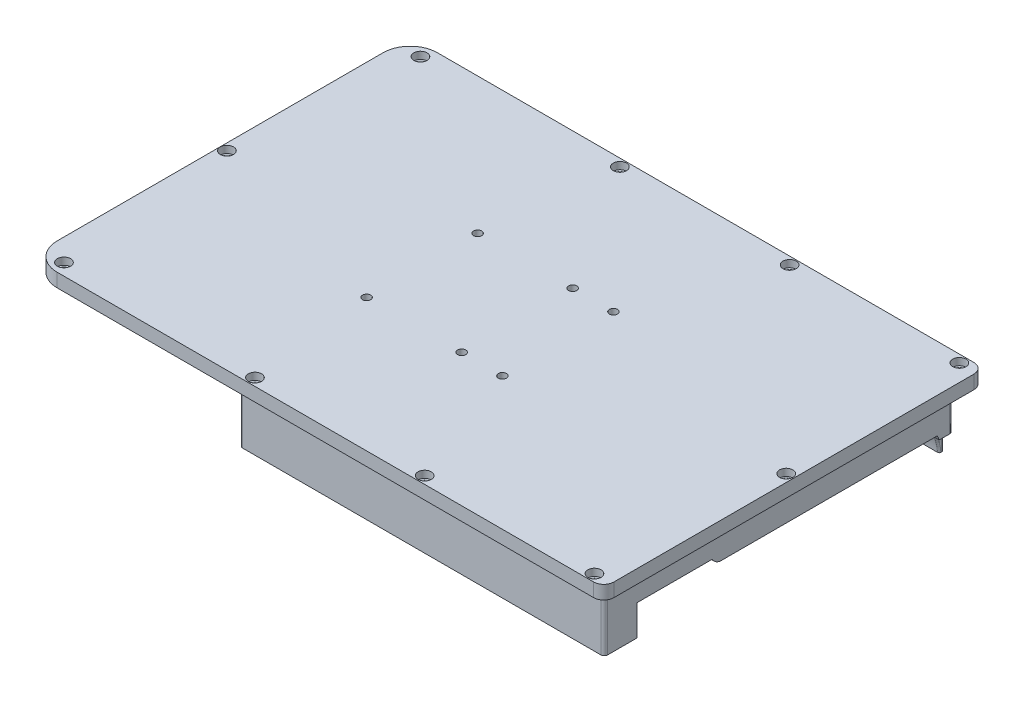
SolidWorks part; units mm, degrees
ref_plane "Front Plane" through (0, 0, 0) normal (0, 0, 1) x (1, 0, 0)
ref_plane "Top Plane" through (0, 0, 0) normal (0, 1, 0) x (1, 0, 0)
ref_plane "Right Plane" through (0, 0, 0) normal (1, 0, 0) x (0, 0, -1)
sketch "Sketch1" plane through (0, 0, 0) normal (0, 1, 0) x (1, 0, 0)
  line L1 (-56, 51.85) -> (56, 51.85)
  line L2 (-56, 51.85) -> (-56, -51.85)
  line L3 (-56, -51.85) -> (56, -51.85)
  line L4 (56, 51.85) -> (56, -51.85)
  line L5 (-56, 51.85) -> (56, -51.85) construction
  line L6 (-56, -51.85) -> (56, 51.85) construction
  point P0 (0, 0)
  dimension "D1" = 103.7
  dimension "D2" = 112
extrude "Boss-Extrude1" add sketch "Sketch1" along normal blind 18.2
ref_plane "Plane1" through (51.5, 0, 0) normal (1, 0, 0) x (0, 0, -1)
sketch "Sketch2" plane through (51.5, 0, 0) normal (1, 0, 0) x (0, 0, -1)
  line L0 (-51.85, 18.2) -> (51.85, 18.2) construction
  line L1 (0, 0) -> (0, -18.713) construction
  circle A0 centre (0, 18.2) radius 16.325
  circle A1 centre (32.65, 18.2) radius 16.325
  circle A2 centre (-32.65, 18.2) radius 16.325
  dimension "D1" = 32.65
  dimension "D2" = 32.65
extrude "Cut-Extrude1" cut sketch "Sketch2" against normal blind 73 contours A0 | A2 | A1 region at (51.5, 18.2, 0) region at (51.5, 18.2, 32.65) region at (51.5, 18.2, -32.65)
fillet "Fillet1" radius 3 2 edges at (15, 18.2, -16.325) (15, 18.2, 16.325)
sketch "Sketch3" plane through (0, 0, 0) normal (0, 0, 1) x (1, 0, 0)
  line L0 (56, 18.2) -> (-56, 18.2) construction
  circle A0 centre (-39, 18.2) radius 16.325
  dimension "D1" = 32.65
  dimension "D2" = 39
extrude "Cut-Extrude2" cut sketch "Sketch3" against normal blind 35.4 and the other way blind 35.4
sketch "Sketch4" plane through (0, 0, -35.4) normal (0, 0, 1) x (1, 0, 0)
  line L0 (-45, 18.2) -> (-45, 9.2)
  line L1 (-55.325, 18.2) -> (-22.675, 18.2) construction
  line L2 (-45, 18.2) -> (-22.675, 18.2)
  line L3 (-45, 9.2) -> (-25.38, 9.2)
  arc A0 (-55.325, 18.2) -> (-22.675, 18.2) centre (-39, 18.2) ccw construction
  arc A1 (-25.38, 9.2) -> (-22.675, 18.2) centre (-39, 18.2) ccw
  dimension "D1" = 9
  dimension "D2" = 6
extrude "Cut-Extrude3" cut sketch "Sketch4" against normal blind 11
mirror "Mirror1" about plane through (0, 0, 0) normal (0, 0, 1) of "Cut-Extrude3"
sketch "Sketch5" plane through (-21.5, 0, 0) normal (1, 0, 0) x (0, 0, -1)
  line L0 (-41.65, 18.2) -> (-41.65, 9.2)
  line L1 (-48.975, 18.2) -> (-16.325, 18.2) construction
  line L2 (-41.65, 9.2) -> (-19.03, 9.2)
  line L3 (-46.4, 9.2) -> (-35.4, 9.2) construction
  line L4 (-41.65, 18.2) -> (-16.325, 18.2)
  line L5 (-16.325, 18.2) -> (16.325, 18.2) construction
  arc A0 (-48.975, 18.2) -> (-18.8593, 9.4638) centre (-32.65, 18.2) ccw construction
  arc A1 (-19.03, 9.2) -> (-18.8593, 9.4638) centre (-32.65, 18.2) ccw
  arc A2 (-18.8593, 9.4638) -> (-16.325, 18.2) centre (-32.65, 18.2) ccw
  dimension "D1" = 9
extrude "Cut-Extrude4" cut sketch "Sketch5" against normal blind 10
fillet "Fillet3" radius 1 8 edges at (-23.3659, 13.5011, 17.0159) (-23.3659, 13.5011, 41.65) (-23.3659, 13.5011, 46.4) (-45, 13.7, 46.4) (-45, 13.7, 35.4) (-23.3659, 13.5011, -46.4) (-45, 13.7, -35.4) (-45, 13.7, -46.4)
sketch "Sketch6" plane through (-45, 0, 0) normal (1, 0, 0) x (0, 0, -1)
  line L0 (45.4, 18.2) -> (36.4, 18.2) construction
  line L2 (46.4, 18.2) -> (46.4, 9.2) construction
  circle A0 centre (42.9, 18.2) radius 3.5
  dimension "D1" = 7
extrude "Cut-Extrude6" cut sketch "Sketch6" against normal through all and the other way blind 1
sketch "Sketch7" plane through (-21.5, 0, 0) normal (1, 0, 0) x (0, 0, -1)
  line L0 (47.231, 10.8583) -> (-16.325, 10.8583)
  arc A0 (18.8593, 9.4638) -> (48.975, 18.2) centre (32.65, 18.2) ccw construction
  arc A1 (18.8593, 9.4638) -> (13.7907, 9.4638) centre (16.325, 7.8583) ccw construction
  arc A2 (-13.7907, 9.4638) -> (13.7907, 9.4638) centre (0, 18.2) ccw construction
  arc A3 (18.8593, 9.4638) -> (47.231, 10.8583) centre (32.65, 18.2) ccw
  arc A4 (18.8593, 9.4638) -> (13.7907, 9.4638) centre (16.325, 7.8583) ccw
  arc A5 (-13.7907, 9.4638) -> (13.7907, 9.4638) centre (0, 18.2) ccw
  arc A6 (-13.7907, 9.4638) -> (-18.8593, 9.4638) centre (-16.325, 7.8583) ccw construction
  arc A7 (-13.7907, 9.4638) -> (-16.325, 10.8583) centre (-16.325, 7.8583) ccw
  arc M4 (-18.8593, 9.4638) -> (-13.7907, 9.4638) centre (-16.325, 7.8583) cw
  arc M5 (-13.7907, 9.4638) -> (13.7907, 9.4638) centre (0, 18.2) ccw
  arc M6 (13.7907, 9.4638) -> (18.8593, 9.4638) centre (16.325, 7.8583) cw
  arc M7 (18.8593, 9.4638) -> (48.975, 18.2) centre (32.65, 18.2) ccw
extrude "Boss-Extrude2" add sketch "Sketch7" along normal blind 1.1 contours L0 M7 M6 | L0 M6 M4 M5 region at (-21.5, 7.1725, -32.613) region at (-21.5, 7.1809, 0)
ref_plane "Plane2" through (15, 0, 0) normal (1, 0, 0) x (0, 0, -1)
mirror "Mirror2" about plane through (15, 0, 0) normal (1, 0, 0) of "Boss-Extrude2"
sketch "Sketch8" plane through (-21.5, 0, 0) normal (1, 0, 0) x (0, 0, -1)
  line L3 (-19.03, 9.2) -> (-41.65, 9.2)
  line L4 (-41.65, 9.2) -> (-41.65, 18.2)
  line L5 (-41.65, 9.2) -> (-41.65, 18.2)
  line L6 (-19.03, 9.2) -> (-41.65, 9.2)
  line L9 (-41.65, 18.2) -> (-48.975, 18.2)
  line L20 (-41.65, 18.2) -> (-48.975, 18.2)
  arc A1 (-48.975, 18.2) -> (-19.03, 9.2) centre (-32.65, 18.2) ccw
  arc A2 (-48.975, 18.2) -> (-19.03, 9.2) centre (-32.65, 18.2) ccw
  dimension "D1" = 0
extrude "Boss-Extrude3" add sketch "Sketch8" along normal up to surface (1.1 mm away) up to face at (-20.4, 8.4267, 0)
mirror "Mirror3" about plane through (15, 0, 0) normal (1, 0, 0) of "Boss-Extrude3"
sketch "Sketch10" plane through (0, 18.2, 0) normal (0, 1, 0) x (1, 0, 0)
  line L0 (51.5, -55) -> (51.5, 55) construction
  line L1 (50.4, 47.231) -> (51.5, 47.231)
  line L2 (50.4, 47.231) -> (50.4, 50.1549)
  line L3 (50.4, 56.7433) -> (51.5, 56.7433)
  line L4 (51.5, 47.231) -> (51.5, 56.7433)
  line L5 (56, 51.85) -> (-56, 51.85) construction
  line L6 (50.4, 50.1549) -> (25.4, 50.1549)
  line L8 (50.4, 51.85) -> (25.4, 51.85)
  line L9 (25.4, 50.1549) -> (25.4, 51.85)
  line L10 (50.4, 51.85) -> (50.4, 56.7433)
  dimension "D1" = 2.9239
  dimension "D2" = 25
extrude "Cut-Extrude9" cut sketch "Sketch10" against normal blind 6
sketch "Sketch11" plane through (0, 18.2, 0) normal (0, 1, 0) x (1, 0, 0)
  line L6 (51.5, 51.85) -> (56, 51.85)
  line L7 (51.5, 51.85) -> (51.5, -51.85)
  line L8 (51.5, -51.85) -> (56, -51.85)
  line L9 (56, 51.85) -> (56, -51.85)
sketch "Sketch13" plane through (-56, 0, 0) normal (-1, 0, 0) x (0, 0, 1)
  line L1 (-51.85, 18.2) -> (-48.975, 18.2)
  line L2 (-51.85, 18.2) -> (-51.85, 16.7)
  line L3 (-51.85, 16.7) -> (-48.9059, 16.7)
  line L7 (-47.231, 10.8583) -> (16.325, 10.8583)
  line L8 (-16.325, 18.2) -> (-48.975, 18.2)
  line L9 (16.325, 18.2) -> (-16.325, 18.2)
  arc A3 (18.8593, 9.4638) -> (16.325, 10.8583) centre (16.325, 7.8583) ccw
  arc A4 (-48.975, 18.2) -> (-47.231, 10.8583) centre (-32.65, 18.2) ccw
  arc A5 (16.325, 18.2) -> (18.8593, 9.4638) centre (32.65, 18.2) ccw
  arc A7 (-48.975, 18.2) -> (-48.9059, 16.7) centre (-32.65, 18.2) ccw
  dimension "D2" = 1.5
  dimension "D1" = 0
sketch "Sketch15" plane through (0, 0, 51.85) normal (0, 0, 1) x (1, 0, 0)
  line L6 (-56, 0) -> (56, 0)
  line L7 (56, 0) -> (56, 18.2)
  line L10 (56, 18.2) -> (-56, 18.2)
  line L11 (-56, 18.2) -> (-56, 0)
  line L12 (-56, 0) -> (56, 0)
  line L13 (56, 0) -> (56, 18.2)
  line L16 (56, 18.2) -> (-56, 18.2)
  line L17 (-56, 18.2) -> (-56, 0)
  dimension "D1" = 0
extrude "Cut-Extrude12" cut sketch "Sketch15" against normal blind 1
extrude "Cut-Extrude13" cut sketch "Sketch13" against normal up to surface (107.5 mm away) up to face at (51.5, 13.3726, -5.5532)
fillet "Fillet9" radius 0.5 12 edges at (25.4, 14.45, -51.85) (25.4, 14.45, -50.1549) (-20.4, 13.7, 41.65) (-56, 17.4492, -48.9577) (-21.5, 17.4492, -48.9577) (50.4, 13.7, 41.65) (51.5, 13.7, 41.65) (50.4, 14.4118, -48.5294) (50.4, 14.45, -50.1549) (-44.9033, 16.2839, -45.8289) (-45, 14.9596, -41.5771) (-56, 14.7, -42.9)
mirror "Mirror4" about plane through (0, 0, 0) normal (0, 1, 0) of bodies 118
delete or keep bodies "Body-Delete/Keep 1" type delete bodies bodies 118
sketch "Sketch16" plane through (0, 0, 0) normal (0, 1, 0) x (1, 0, 0)
  line L13 (56, 52) -> (56, 56.5)
  line L14 (56, 56.5) -> (-105, 56.5)
  line L15 (-113, 48.5) -> (-113, -47.5)
  line L16 (-105, -55.5) -> (56, -55.5)
  line L17 (56, -55.5) -> (56, -51)
  line L20 (-108.9199, 43.263) -> (-109, 43.263)
  line L23 (56, -51) -> (56, 52)
  arc A18 (-105, 56.5) -> (-113, 48.5) centre (-105, 48.5) ccw
  arc A19 (-113, -47.5) -> (-105, -55.5) centre (-105, -47.5) ccw
  circle A23 centre (51, 54.25) radius 1
  circle A24 centre (1, 54.25) radius 1
  circle A25 centre (-49, 54.25) radius 1
  circle A26 centre (-106.5, 53) radius 1
  circle A27 centre (-111, 0.5) radius 1
  circle A28 centre (-106.5, -52) radius 1
  circle A29 centre (-49, -53.25) radius 1
  circle A30 centre (1, -53.25) radius 1
  circle A31 centre (51, -53.25) radius 1
  line M1 (-56, -50.85) -> (56, -50.85)
  line M2 (56, -50.85) -> (56, 51.85)
  line M3 (56, 51.85) -> (-56, 51.85)
  line M4 (-56, 51.85) -> (-56, -50.85)
extrude "Boss-Extrude5" add sketch "Sketch16" along normal blind 4 contours M4 M1 M2 M3 | L15 A19 L16 L17 L13 L14 A18 A31 A30 A29 A28 A27 A26 A25 A24 A23 region at (-72.6465, 0, -0.5) region at (0, 0, -0.5)
sketch "Sketch18" plane through (0, -18.2, 0) normal (0, -1, 0) x (1, 0, 0)
  line L1 (56, 50.85) -> (51.5, 50.85)
  line L2 (56, 50.85) -> (56, -52)
  line L3 (56, -52) -> (51.5, -52)
  line L4 (51.5, 50.85) -> (51.5, -52)
  dimension "D1" = 4.5
extrude "Cut-Extrude14" cut sketch "Sketch18" against normal up to surface (18.2 mm away) up to face at (51, 0, 54.25)
fillet "Fillet10" radius 1 4 edges at (-56, -9.1, 50.85) (-56, -8.35, -51.85) (51.5, -6.1, -51.85) (51.5, -9.1, 50.85)
fillet "Fillet11" radius 3 2 edges at (56, 2, 55.5) (56, 2, -56.5)
sketch "Sketch23" plane through (0, 0, 0) normal (0, -1, 0) x (1, 0, 0)
  line L0 (56, 52.5) -> (56, -53.5) construction
  line L1 (53, -56.5) -> (-105, -56.5) construction
  circle A0 centre (53.75, -0.5) radius 1.1
  dimension "D1" = 2.2
  dimension "D2" = 2.25
  dimension "D3" = 56
extrude "Cut-Extrude18" cut sketch "Sketch23" against normal blind 10
sketch "Sketch19" plane through (0, 4, 0) normal (0, 1, 0) x (1, 0, 0)
  circle A0 centre (1, 54.25) radius 1.95
  circle A1 centre (51, -53.25) radius 1.95
  circle A2 centre (51, 54.25) radius 1.95
  circle A3 centre (1, -53.25) radius 1.95
  circle A4 centre (-49, -53.25) radius 1.95
  circle A5 centre (-106.5, -52) radius 1.95
  circle A6 centre (-111, 0.5) radius 1.95
  circle A7 centre (-106.5, 53) radius 1.95
  circle A9 centre (53.75, 0.5) radius 1.95
  circle A10 centre (-49, 54.25) radius 1.95
  dimension "D1" = 3.9
extrude "Cut-Extrude15" cut sketch "Sketch19" against normal blind 2.1
fillet "Fillet13" radius 0.4 10 edges at (-106.5, 1.9, 53) (-111, 1.9, 0.5) (-106.5, 1.9, -52) (-49, 1.9, -53.25) (-49, 1.9, 54.25) (1, 1.9, 54.25) (1, 1.9, -53.25) (51, 1.9, -53.25) (51, 1.9, 54.25) (53.75, 1.9, 0.6)
sketch "Sketch21" plane through (0, 4, 0) normal (0, 1, 0) x (1, 0, 0)
  line L0 (-13, -16.35) -> (-53, -16.35) construction
  line L1 (-53, -16.35) -> (-53, 16.35) construction
  line L2 (-53, 16.35) -> (-13, 16.35) construction
  line L3 (-13, 16.35) -> (-13, -16.35) construction
  line L4 (0, 0) -> (-13, 0) construction
  circle A0 centre (-13, -16.35) radius 1.2
  circle A1 centre (-13, 16.35) radius 1.2
  circle A2 centre (-53, -16.35) radius 1.2
  circle A3 centre (-53, 16.35) radius 1.2
  circle A4 centre (-25, -16.35) radius 1.2
  circle A5 centre (-25, 16.35) radius 1.2
  dimension "D1" = 2.4
  dimension "D5" = 28
  dimension "D2" = 32.7
  dimension "D3" = 40
  dimension "D4" = 13
extrude "Cut-Extrude16" cut sketch "Sketch21" against normal blind 10
sketch "Sketch22" plane through (0, 0, 0) normal (0, -1, 0) x (1, 0, 0)
  circle A0 centre (-106.5, -53) radius 1.1
  circle A1 centre (-111, -0.5) radius 1.1
  circle A2 centre (-106.5, 52) radius 1.1
  circle A3 centre (-49, 53.25) radius 1.1
  circle A4 centre (1, 53.25) radius 1.1
  circle A5 centre (51, 53.25) radius 1.1
  circle A6 centre (51, -54.25) radius 1.1
  circle A7 centre (1, -54.25) radius 1.1
  circle A8 centre (-49, -54.25) radius 1.1
  dimension "D1" = 2.2
extrude "Cut-Extrude17" cut sketch "Sketch22" against normal through all both and the other way through all
